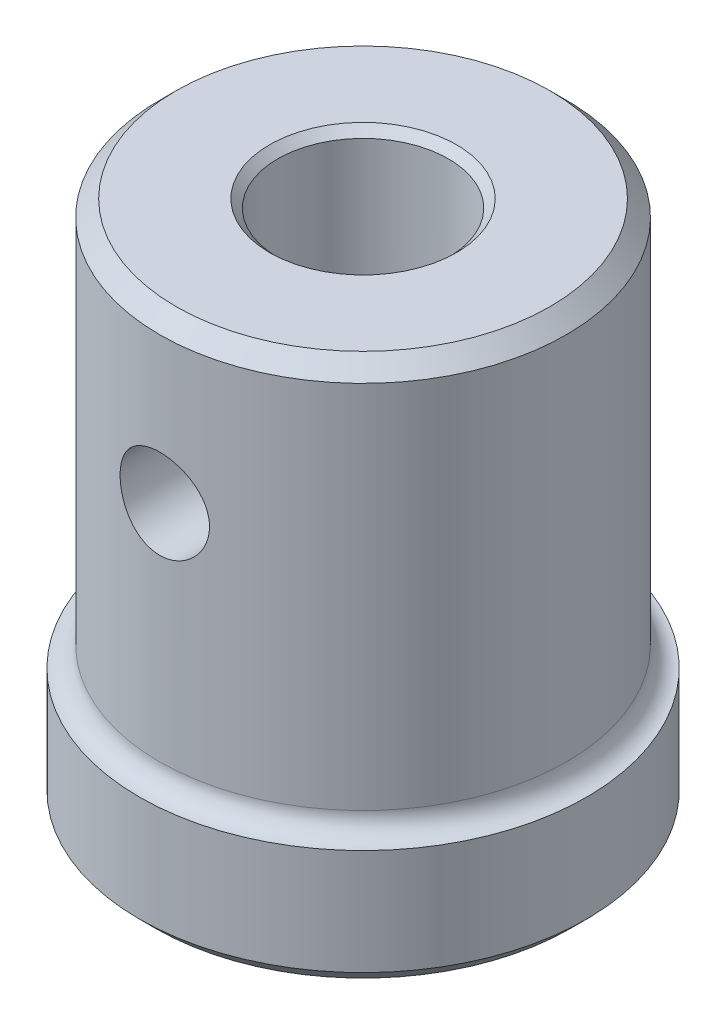
SolidWorks part; units mm, degrees
material "1.0060 (E335)"
ref_plane "Front Plane" through (0, 0, 0) normal (0, 0, 1) x (1, 0, 0)
ref_plane "Top Plane" through (0, 0, 0) normal (0, 1, 0) x (1, 0, 0)
ref_plane "Right Plane" through (0, 0, 0) normal (1, 0, 0) x (0, 0, -1)
sketch "Sketch1" plane through (0, 0, 0) normal (0, 1, 0) x (1, 0, 0)
  circle A0 centre (0, 0) radius 27.5
  dimension "D1" = 55
extrude "Boss-Extrude1" add sketch "Sketch1" along normal blind 15
sketch "Sketch2" plane through (0, 15, 0) normal (0, 1, 0) x (1, 0, 0)
  circle A0 centre (0, 0) radius 25
  dimension "D1" = 50
extrude "Boss-Extrude2" add sketch "Sketch2" along normal blind 50
sketch "Sketch3" plane through (0, 65, 0) normal (0, 1, 0) x (1, 0, 0)
  circle A0 centre (0, 0) radius 10.5
  dimension "D1" = 21
extrude "Cut-Extrude1" cut sketch "Sketch3" against normal blind 50
chamfer "Chamfer1" distance 2 angle 45 2 edges at (0, 65, 25) (0, 0, 27.5)
chamfer "Chamfer2" distance 1 angle 45 1 edges at (0, 65, 10.5)
fillet "Fillet1" radius 2.5 1 edges at (0, 15, 25)
sketch "Sketch4" plane through (0, 0, 0) normal (0, 0, 1) x (1, 0, 0)
  line L0 (0, -1000) -> (0, 49000) construction
  line L1 (0, 18) -> (-10.5, 18)
  line L2 (0, 15) -> (-10.5, 15)
  line L3 (0, 15) -> (0, 18)
  arc A0 (-10.5, 15) -> (-10.5, 18) centre (-10.5, 16.5) cw
  dimension "D1" = 3
  dimension "D2" = 21
  dimension "D3" = 15
revolve "Cut-Revolve1" cut sketch "Sketch4" angle 360 about L0
sketch "Sketch5" plane through (0, 0, 0) normal (0, 0, 1) x (1, 0, 0)
  line L0 (23, 65) -> (-23, 65) construction
  circle A0 centre (0, 45) radius 5.5
  dimension "D1" = 11
  dimension "D2" = 20
extrude "Cut-Extrude2" cut sketch "Sketch5" against normal through all both and the other way through all
